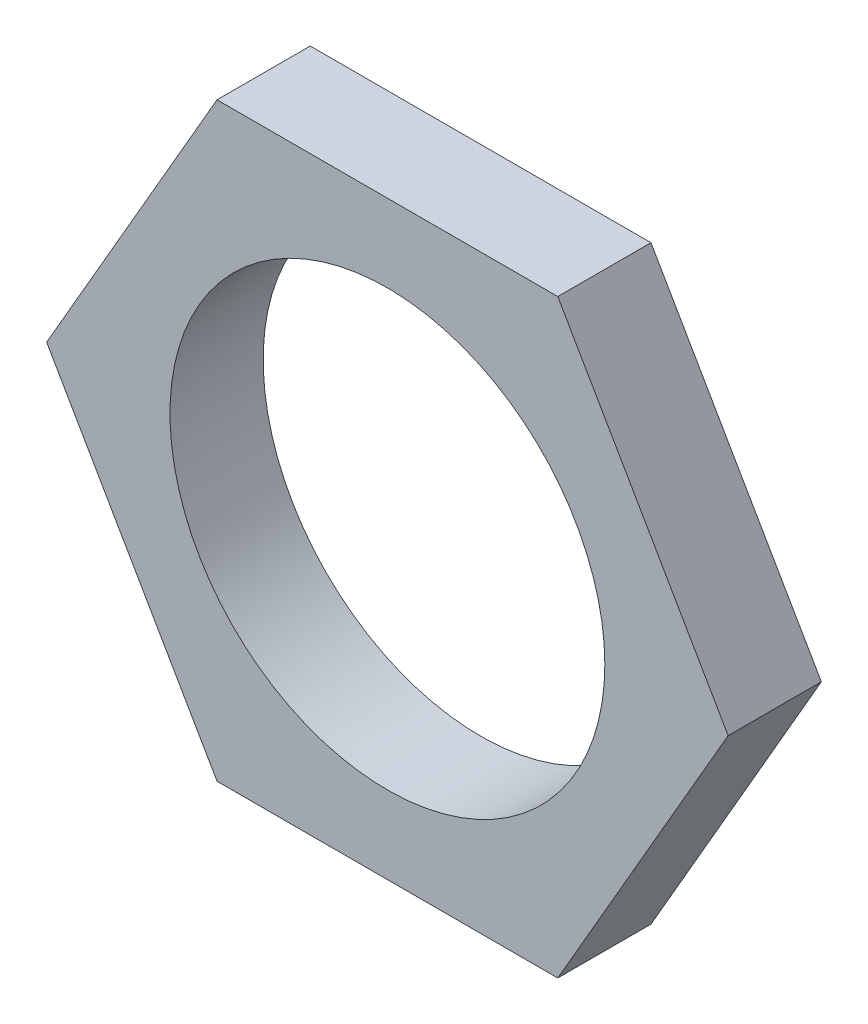
SolidWorks part; units mm, degrees
ref_plane "Front Plane" through (0, 0, 0) normal (0, 0, 1) x (1, 0, 0)
ref_plane "Top Plane" through (0, 0, 0) normal (0, 1, 0) x (1, 0, 0)
ref_plane "Right Plane" through (0, 0, 0) normal (1, 0, 0) x (0, 0, -1)
sketch "Sketch1" plane through (0, 0, 0) normal (0, 0, 1) x (1, 0, 0)
  line L1 (-5.4848, 0) -> (-2.7424, -4.75)
  line L2 (-2.7424, -4.75) -> (2.7424, -4.75)
  line L3 (2.7424, -4.75) -> (5.4848, 0)
  line L4 (5.4848, 0) -> (2.7424, 4.75)
  line L5 (2.7424, 4.75) -> (-2.7424, 4.75)
  line L6 (-2.7424, 4.75) -> (-5.4848, 0)
  circle A0 centre (0, 0) radius 4.75 construction
  dimension "D2" = 4.75
  dimension "D1" = 9.5
extrude "Boss-Extrude1" add sketch "Sketch1" along normal blind 1.5
sketch "Sketch2" plane through (0, 0, 1.5) normal (0, 0, 1) x (1, 0, 0)
  circle A0 centre (0, 0) radius 3.5
  dimension "D1" = 7
extrude "Cut-Extrude1" cut sketch "Sketch2" against normal blind 1.5
